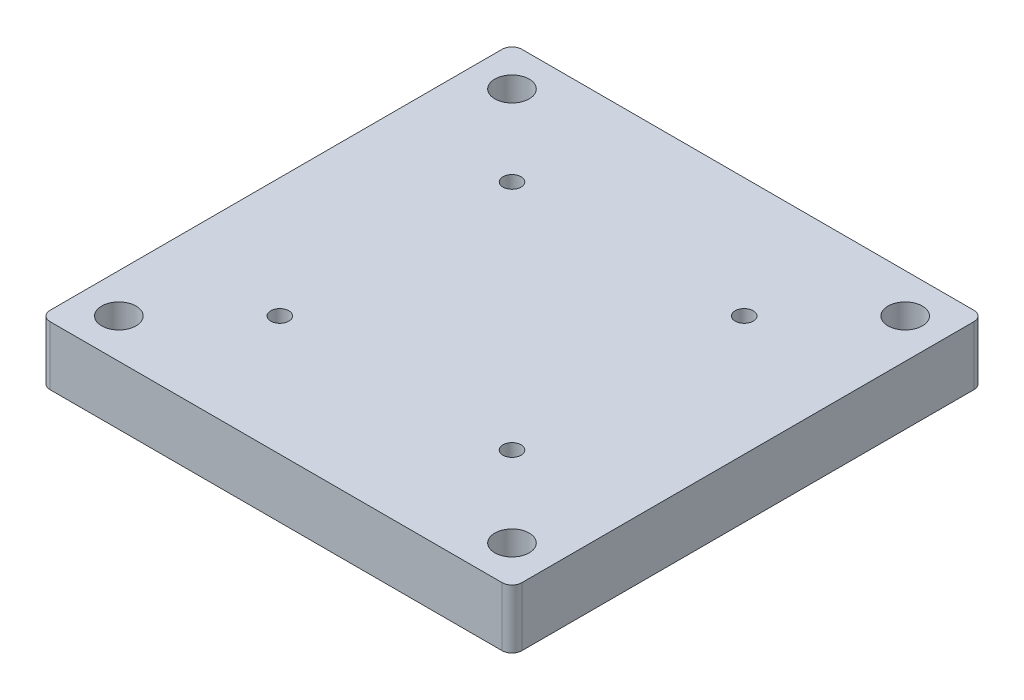
SolidWorks part; units mm, degrees
material "Delrin 2700 NC010, Low Viscosity Acetal Copolymer (SS)"
ref_plane "Front" through (0, 0, 0) normal (0, 0, 1) x (1, 0, 0)
ref_plane "Top" through (0, 0, 0) normal (0, 1, 0) x (1, 0, 0)
ref_plane "Right" through (0, 0, 0) normal (1, 0, 0) x (0, 0, -1)
sketch "Sketch1" plane through (0, 0, 0) normal (0, 1, 0) x (1, 0, 0)
  line L1 (-76.2, 76.2) -> (76.2, 76.2)
  line L2 (-76.2, 76.2) -> (-76.2, -76.2)
  line L3 (-76.2, -76.2) -> (76.2, -76.2)
  line L4 (76.2, 76.2) -> (76.2, -76.2)
  line L5 (-76.2, 76.2) -> (76.2, -76.2) construction
  line L6 (-76.2, -76.2) -> (76.2, 76.2) construction
  point P0 (0, 0)
  dimension "D1" = 152.4
  dimension "D2" = 152.4
extrude "Boss-Extrude1" add sketch "Sketch1" along normal blind 19.05
hole_wizard "CBORE for 1/4 Socket Head Cap Screw1" positions "Sketch2" profile "Sketch3" counterbore size "1/4" standard "ANSI Inch" end condition through all
sketch "Sketch2" plane through (0, 19.05, 0) normal (0, 1, 0) x (1, 0, 0)
  line L1 (-63.5, 63.5) -> (63.5, 63.5) construction
  line L2 (-63.5, 63.5) -> (-63.5, -63.5) construction
  line L3 (-63.5, -63.5) -> (63.5, -63.5) construction
  line L4 (63.5, 63.5) -> (63.5, -63.5) construction
  line L5 (-63.5, 63.5) -> (63.5, -63.5) construction
  line L6 (-63.5, -63.5) -> (63.5, 63.5) construction
  point P0 (-63.5, 63.5)
  point P2 (63.5, 63.5)
  point P4 (63.5, -63.5)
  point P6 (-63.5, -63.5)
  point P108 (0, 0)
  dimension "D1" = 127
  dimension "D2" = 127
sketch "Sketch3" plane through (-63.5, 19.05, -63.5) normal (1, 0, 0) x (0, 0, 1)
  line L0 (0, 0) -> (0, 19.05)
  line L1 (0, 19.05) -> (3.2639, 19.05)
  line L3 (3.2639, 19.05) -> (3.2639, 8.89)
  line L4 (3.2639, 8.89) -> (5.5562, 8.89)
  line L5 (5.5562, 8.89) -> (5.5562, 0)
  line L7 (5.5562, 0) -> (0, 0)
  line L11 (0, -6.35) -> (0, 107.95) construction
  dimension "Thru Hole Dia." = 6.5278
  dimension "Thru Hole Depth" = 19.05
  dimension "C'Bore Dia." = 11.1125
  dimension "C'Bore Depth" = 8.89
sketch "Sketch4" plane through (0, 0, 76.2) normal (0, 0, 1) x (1, 0, 0)
  line L0 (-31.9484, 19.05) -> (-31.9484, 12.7)
  line L1 (-76.2, 19.05) -> (76.2, 19.05) construction
  line L2 (-31.9484, 12.7) -> (-35.7188, 12.7)
  line L3 (-35.7188, 12.7) -> (-35.7188, 6.7469)
  line L4 (-35.7188, 6.7469) -> (-21.4312, 6.7469)
  line L5 (-21.4312, 6.7469) -> (-21.4312, 12.7)
  line L6 (-21.4312, 12.7) -> (-25.2016, 12.7)
  line L7 (-25.2016, 12.7) -> (-25.2016, 19.05)
  line L8 (0, 0) -> (0, 19.05) construction
  line L9 (-28.575, 6.7469) -> (-28.575, 19.05) construction
  line L10 (28.575, 6.7469) -> (28.575, 19.05) construction
  line L11 (25.2016, 12.7) -> (25.2016, 19.05)
  line L12 (21.4312, 12.7) -> (25.2016, 12.7)
  line L13 (21.4312, 6.7469) -> (21.4312, 12.7)
  line L14 (35.7188, 6.7469) -> (21.4312, 6.7469)
  line L15 (35.7188, 12.7) -> (35.7188, 6.7469)
  line L16 (31.9484, 12.7) -> (35.7188, 12.7)
  line L17 (31.9484, 19.05) -> (31.9484, 12.7)
  line L18 (-31.9484, 19.05) -> (-25.2016, 19.05)
  line L19 (25.2016, 19.05) -> (31.9484, 19.05)
  line L20 (-76.2, 0) -> (76.2, 0) construction
  dimension "D1" = 14.2875
  dimension "D2" = 6.7469
  dimension "D3" = 6.35
  dimension "D4" = 57.15
  dimension "D5" = 5.9531
  dimension "D6" = 6.7469
extrude "T-SLOT CUT WITH MCMASTER 8789A16 BIT" [suppressed] cut sketch "Sketch4" against normal through all
fillet "Fillet1" radius 3.175 4 edges at (-76.2, 9.525, 76.2) (76.2, 9.525, 76.2) (76.2, 9.525, -76.2) (-76.2, 9.525, -76.2)
hole_wizard "CBORE for #10 Button Head Cap Screw1" positions "Sketch5" profile "Sketch6" counterbore size "#10" standard "ANSI Inch" end condition through all
sketch "Sketch5" plane through (0, 0, 0) normal (0, -1, 0) x (-1, 0, 0)
  line L1 (37.5, -37.5) -> (-37.5, -37.5) construction
  line L2 (37.5, -37.5) -> (37.5, 37.5) construction
  line L3 (37.5, 37.5) -> (-37.5, 37.5) construction
  line L4 (-37.5, -37.5) -> (-37.5, 37.5) construction
  line L5 (37.5, -37.5) -> (-37.5, 37.5) construction
  line L6 (37.5, 37.5) -> (-37.5, -37.5) construction
  point P0 (37.5, -37.5)
  point P2 (-37.5, -37.5)
  point P4 (37.5, 37.5)
  point P6 (-37.5, 37.5)
  point P61 (37.5, -37.5)
  point P62 (-37.5, -37.5)
  point P63 (-37.5, 37.5)
  point P64 (37.5, 37.5)
  point P65 (0, 0)
  point P66 (54.3656, -43.6879)
  dimension "D1" = 75
  dimension "D2" = 75
sketch "Sketch6" plane through (-37.5, 0, 37.5) normal (1, 0, 0) x (0, 0, -1)
  line L0 (0, 0) -> (0, 19.05)
  line L1 (0, 19.05) -> (2.921, 19.05)
  line L3 (2.921, 19.05) -> (2.921, 7.874)
  line L4 (2.921, 7.874) -> (5.2705, 7.874)
  line L5 (5.2705, 7.874) -> (5.2705, 0)
  line L7 (5.2705, 0) -> (0, 0)
  line L11 (0, -6.35) -> (0, 107.95) construction
  dimension "Thru Hole Dia." = 5.842
  dimension "Thru Hole Depth" = 19.05
  dimension "C'Bore Dia." = 10.541
  dimension "C'Bore Depth" = 7.874
